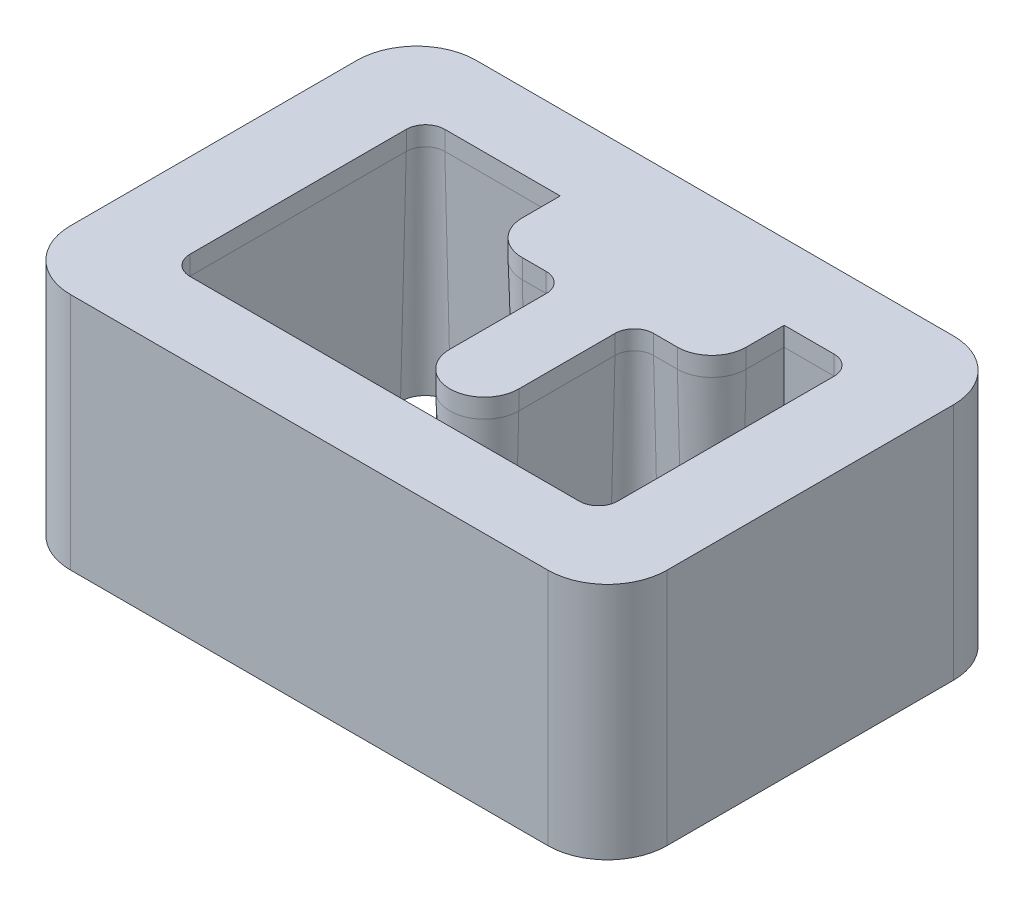
SolidWorks part; units mm, degrees
material "K110"
ref_plane "Front Plane" through (0, 0, 0) normal (0, 0, 1) x (1, 0, 0)
ref_plane "Top Plane" through (0, 0, 0) normal (0, 1, 0) x (1, 0, 0)
ref_plane "Right Plane" through (0, 0, 0) normal (1, 0, 0) x (0, 0, -1)
sketch "Sketch1" plane through (0, 0, 0) normal (0, 1, 0) x (1, 0, 0)
  line L1 (-50, -34) -> (50, -34)
  line L2 (-50, -34) -> (-50, 34)
  line L3 (-50, 34) -> (50, 34)
  line L4 (50, -34) -> (50, 34)
  line L5 (-50, -34) -> (50, 34) construction
  line L6 (-50, 34) -> (50, -34) construction
  point P0 (0, 0)
  dimension "D1" = 68
  dimension "D2" = 100
extrude "Boss-Extrude1" add sketch "Sketch1" against normal blind 40
fillet "Fillet1" radius 10 4 edges at (-50, -20, -34) (50, -20, -34) (50, -20, 34) (-50, -20, 34)
sketch "Sketch2" plane through (0, 0, 0) normal (0, 1, 0) x (1, 0, 0)
  line L22 (-32.625, -21.36) -> (32.625, -21.36)
  line L23 (-35.855, 18.13) -> (-35.855, -18.13)
  line L24 (-13.275, 21.36) -> (-32.625, 21.36)
  line L25 (-13.275, 15) -> (-13.275, 21.36)
  line L26 (-3.505, 9.23) -> (-7.505, 9.23)
  line L27 (-0.275, -10.13) -> (-0.275, 6)
  line L28 (11.265, 6) -> (11.265, -10.13)
  line L29 (18.495, 9.23) -> (14.495, 9.23)
  line L30 (24.265, 21.36) -> (24.265, 15)
  line L31 (32.625, 21.36) -> (24.265, 21.36)
  line L32 (35.855, -18.13) -> (35.855, 18.13)
  line L33 (-32.625, -21.36) -> (32.625, -21.36)
  line L34 (-35.855, 18.13) -> (-35.855, -18.13)
  line L35 (-13.275, 21.36) -> (-32.625, 21.36)
  line L36 (-13.275, 15) -> (-13.275, 21.36)
  line L37 (-3.505, 9.23) -> (-7.505, 9.23)
  line L38 (-0.275, -10.13) -> (-0.275, 6)
  line L39 (11.265, 6) -> (11.265, -10.13)
  line L40 (18.495, 9.23) -> (14.495, 9.23)
  line L41 (24.265, 21.36) -> (24.265, 15)
  line L42 (32.625, 21.36) -> (24.265, 21.36)
  line L43 (35.855, -18.13) -> (35.855, 18.13)
  arc A18 (32.625, -21.36) -> (35.855, -18.13) centre (32.625, -18.13) ccw
  arc A19 (-35.855, -18.13) -> (-32.625, -21.36) centre (-32.625, -18.13) ccw
  arc A20 (-32.625, 21.36) -> (-35.855, 18.13) centre (-32.625, 18.13) ccw
  arc A21 (-13.275, 15) -> (-7.505, 9.23) centre (-7.505, 15) ccw
  arc A22 (-0.275, 6) -> (-3.505, 9.23) centre (-3.505, 6) ccw
  arc A23 (-0.275, -10.13) -> (11.265, -10.13) centre (5.495, -10.13) ccw
  arc A24 (14.495, 9.23) -> (11.265, 6) centre (14.495, 6) ccw
  arc A25 (18.495, 9.23) -> (24.265, 15) centre (18.495, 15) ccw
  arc A26 (35.855, 18.13) -> (32.625, 21.36) centre (32.625, 18.13) ccw
  arc A27 (32.625, -21.36) -> (35.855, -18.13) centre (32.625, -18.13) ccw
  arc A28 (-35.855, -18.13) -> (-32.625, -21.36) centre (-32.625, -18.13) ccw
  arc A29 (-32.625, 21.36) -> (-35.855, 18.13) centre (-32.625, 18.13) ccw
  arc A30 (-13.275, 15) -> (-7.505, 9.23) centre (-7.505, 15) ccw
  arc A31 (-0.275, 6) -> (-3.505, 9.23) centre (-3.505, 6) ccw
  arc A32 (-0.275, -10.13) -> (11.265, -10.13) centre (5.495, -10.13) ccw
  arc A33 (14.495, 9.23) -> (11.265, 6) centre (14.495, 6) ccw
  arc A34 (18.495, 9.23) -> (24.265, 15) centre (18.495, 15) ccw
  arc A35 (35.855, 18.13) -> (32.625, 21.36) centre (32.625, 18.13) ccw
  dimension "D1" = 0.23
extrude "Cut-Extrude1" cut sketch "Sketch2" against normal up to next
sketch "Sketch3" plane through (0, 0, 0) normal (0, 0, 1) x (1, 0, 0)
  line L6 (35.855, -3.2) -> (36.8186, -40)
  line L7 (40, -40) -> (40, 0) construction
  line L8 (40, -40) -> (50, -40) construction
  line L11 (37.4, 0) -> (-37.4, 0) construction
  line L12 (36.8186, -40) -> (34.855, -40)
  line L13 (-40, -40) -> (40, -40) construction
  line L14 (34.855, -3.2) -> (35.855, -3.2)
  line L15 (34.855, -40) -> (34.855, -3.2)
  line L16 (35.855, -40) -> (35.855, 0) construction
  dimension "D1" = 3.2
  dimension "D2" = 1.5
  dimension "D3" = 1
sketch "Sketch5" plane through (0, 0, 0) normal (0, 1, 0) x (1, 0, 0)
  line L0 (32.625, 21.36) -> (24.265, 21.36) construction
  line L1 (35.855, -18.13) -> (35.855, 18.13) construction
  line L2 (24.265, 21.36) -> (24.265, 15) construction
  line L3 (18.495, 9.23) -> (14.495, 9.23) construction
  line L4 (11.265, 6) -> (11.265, -10.13) construction
  line L5 (-0.275, -10.13) -> (-0.275, 6) construction
  line L6 (-3.505, 9.23) -> (-7.505, 9.23) construction
  line L7 (-13.275, 15) -> (-13.275, 21.36) construction
  line L8 (-13.275, 21.36) -> (-32.625, 21.36) construction
  line L9 (-35.855, 18.13) -> (-35.855, -18.13) construction
  line L10 (-32.625, -21.36) -> (32.625, -21.36) construction
  line L11 (-32.625, -21.36) -> (32.625, -21.36)
  line L12 (-35.855, 18.13) -> (-35.855, -18.13)
  line L13 (-13.275, 21.36) -> (-32.625, 21.36)
  line L14 (-13.275, 15) -> (-13.275, 21.36)
  line L15 (-3.505, 9.23) -> (-7.505, 9.23)
  line L16 (-0.275, -10.13) -> (-0.275, 6)
  line L17 (11.265, 6) -> (11.265, -10.13)
  line L18 (18.495, 9.23) -> (14.495, 9.23)
  line L19 (24.265, 21.36) -> (24.265, 15)
  line L20 (35.855, -18.13) -> (35.855, 18.13)
  line L21 (32.625, 21.36) -> (24.265, 21.36)
  arc A0 (-0.275, 6) -> (-3.505, 9.23) centre (-3.505, 6) ccw construction
  arc A1 (35.855, 18.13) -> (32.625, 21.36) centre (32.625, 18.13) ccw construction
  arc A2 (18.495, 9.23) -> (24.265, 15) centre (18.495, 15) ccw construction
  arc A3 (14.495, 9.23) -> (11.265, 6) centre (14.495, 6) ccw construction
  arc A4 (-0.275, -10.13) -> (11.265, -10.13) centre (5.495, -10.13) ccw construction
  arc A5 (-13.275, 15) -> (-7.505, 9.23) centre (-7.505, 15) ccw construction
  arc A6 (-32.625, 21.36) -> (-35.855, 18.13) centre (-32.625, 18.13) ccw construction
  arc A7 (-35.855, -18.13) -> (-32.625, -21.36) centre (-32.625, -18.13) ccw construction
  arc A8 (32.625, -21.36) -> (35.855, -18.13) centre (32.625, -18.13) ccw construction
  arc A9 (32.625, -21.36) -> (35.855, -18.13) centre (32.625, -18.13) ccw
  arc A10 (-35.855, -18.13) -> (-32.625, -21.36) centre (-32.625, -18.13) ccw
  arc A11 (-32.625, 21.36) -> (-35.855, 18.13) centre (-32.625, 18.13) ccw
  arc A12 (-13.275, 15) -> (-7.505, 9.23) centre (-7.505, 15) ccw
  arc A13 (-0.275, 6) -> (-3.505, 9.23) centre (-3.505, 6) ccw
  arc A14 (-0.275, -10.13) -> (11.265, -10.13) centre (5.495, -10.13) ccw
  arc A15 (14.495, 9.23) -> (11.265, 6) centre (14.495, 6) ccw
  arc A16 (18.495, 9.23) -> (24.265, 15) centre (18.495, 15) ccw
  arc A17 (35.855, 18.13) -> (32.625, 21.36) centre (32.625, 18.13) ccw
sweep "Cut-Sweep1" cut profiles "Sketch3" path "Sketch5"
hole_wizard "M6 Tapped Hole1" positions "Sketch11" profile "Sketch9" tap size "M6" standard "ISO"
sketch "Sketch11" plane through (0, -40, 0) normal (0, -1, 0) x (-1, 0, 0)
  line L0 (-40, 34) -> (40, 34) construction
  line L1 (-50, -24) -> (-50, 24) construction
  line L2 (50, 24) -> (50, -24) construction
  line L3 (40, -34) -> (-40, -34) construction
  point P0 (-43, 27)
  point P2 (43, 27)
  point P4 (43, -27)
  point P6 (-43, -27)
  dimension "D1" = 7
  dimension "D2" = 7
  dimension "D3" = 7
  dimension "D4" = 7
sketch "Sketch9" plane through (43, -40, -27) normal (1, 0, 0) x (0, 0, -1)
  line L0 (0, 0) -> (0, 18.5022)
  line L1 (0, 18.5022) -> (2.5, 17)
  line L2 (2.5, 17) -> (2.5, 0.525)
  line L3 (2.5, 0.525) -> (3.025, 0)
  line L5 (3.025, 0) -> (0, 0)
  line L6 (-2.5, 0.525) -> (-3.025, 0) construction
  line L10 (0, 18.5022) -> (-2.5, 17) construction
  line L11 (0, -6.35) -> (0, 107.95) construction
  dimension "Tap Drill Dia." = 5
  dimension "Tap Drill Depth" = 17
  dimension "Near C'Sink Dia." = 6.05
  dimension "Near C'Sink Angle" = 90
  dimension "Drill Angle" = 118
cosmetic thread "Hole Thread1"
cosmetic thread "Hole Thread2"
cosmetic thread "Hole Thread3"
cosmetic thread "Hole Thread4"
